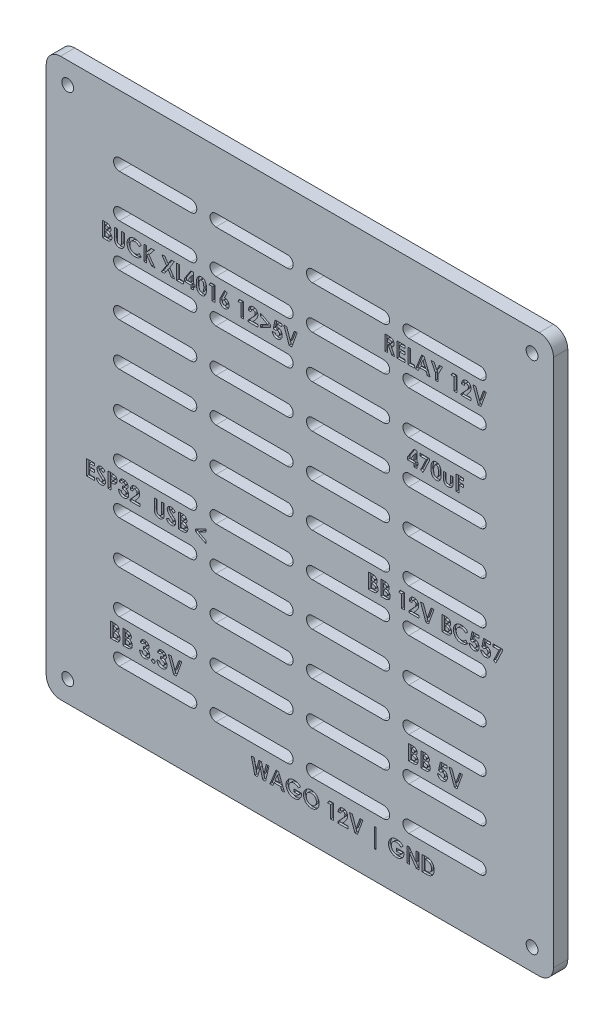
SolidWorks part; units mm, degrees
ref_plane "Front Plane" through (0, 0, 0) normal (0, 0, 1) x (1, 0, 0)
ref_plane "Top Plane" through (0, 0, 0) normal (0, 1, 0) x (1, 0, 0)
ref_plane "Right Plane" through (0, 0, 0) normal (1, 0, 0) x (0, 0, -1)
sketch "Sketch1" plane through (0, 0, 0) normal (0, 0, 1) x (1, 0, 0)
  line L0 (-67, 40) -> (67, 40)
  line L1 (71, 44) -> (71, 192)
  line L2 (67, 196) -> (-67, 196)
  line L3 (-71, 192) -> (-71, 44)
  arc A0 (-71, 44) -> (-67, 40) centre (-67, 44) ccw
  arc A1 (67, 40) -> (71, 44) centre (67, 44) ccw
  arc A2 (71, 192) -> (67, 196) centre (67, 192) ccw
  arc A3 (-67, 196) -> (-71, 192) centre (-67, 192) ccw
extrude "Plate" add sketch "Sketch1" along normal blind 4
sketch "Sketch2" plane through (0, 0, 0) normal (0, 0, 1) x (1, 0, 0)
  line L0 (-50.5, 58) -> (-30.5, 58) construction
  line L1 (-50.5, 59.65) -> (-30.5, 59.65)
  line L2 (-50.5, 56.35) -> (-30.5, 56.35)
  line L3 (-23.5, 58) -> (-3.5, 58) construction
  line L4 (-23.5, 59.65) -> (-3.5, 59.65)
  line L5 (-23.5, 56.35) -> (-3.5, 56.35)
  line L6 (3.5, 58) -> (23.5, 58) construction
  line L7 (3.5, 59.65) -> (23.5, 59.65)
  line L8 (3.5, 56.35) -> (23.5, 56.35)
  line L9 (30.5, 58) -> (50.5, 58) construction
  line L10 (30.5, 59.65) -> (50.5, 59.65)
  line L11 (30.5, 56.35) -> (50.5, 56.35)
  line L12 (-50.5, 70) -> (-30.5, 70) construction
  line L13 (-50.5, 71.65) -> (-30.5, 71.65)
  line L14 (-50.5, 68.35) -> (-30.5, 68.35)
  line L15 (-23.5, 70) -> (-3.5, 70) construction
  line L16 (-23.5, 71.65) -> (-3.5, 71.65)
  line L17 (-23.5, 68.35) -> (-3.5, 68.35)
  line L18 (3.5, 70) -> (23.5, 70) construction
  line L19 (3.5, 71.65) -> (23.5, 71.65)
  line L20 (3.5, 68.35) -> (23.5, 68.35)
  line L21 (30.5, 70) -> (50.5, 70) construction
  line L22 (30.5, 71.65) -> (50.5, 71.65)
  line L23 (30.5, 68.35) -> (50.5, 68.35)
  line L24 (-50.5, 82) -> (-30.5, 82) construction
  line L25 (-50.5, 83.65) -> (-30.5, 83.65)
  line L26 (-50.5, 80.35) -> (-30.5, 80.35)
  line L27 (-23.5, 82) -> (-3.5, 82) construction
  line L28 (-23.5, 83.65) -> (-3.5, 83.65)
  line L29 (-23.5, 80.35) -> (-3.5, 80.35)
  line L30 (3.5, 82) -> (23.5, 82) construction
  line L31 (3.5, 83.65) -> (23.5, 83.65)
  line L32 (3.5, 80.35) -> (23.5, 80.35)
  line L33 (30.5, 82) -> (50.5, 82) construction
  line L34 (30.5, 83.65) -> (50.5, 83.65)
  line L35 (30.5, 80.35) -> (50.5, 80.35)
  line L36 (-50.5, 94) -> (-30.5, 94) construction
  line L37 (-50.5, 95.65) -> (-30.5, 95.65)
  line L38 (-50.5, 92.35) -> (-30.5, 92.35)
  line L39 (-23.5, 94) -> (-3.5, 94) construction
  line L40 (-23.5, 95.65) -> (-3.5, 95.65)
  line L41 (-23.5, 92.35) -> (-3.5, 92.35)
  line L42 (3.5, 94) -> (23.5, 94) construction
  line L43 (3.5, 95.65) -> (23.5, 95.65)
  line L44 (3.5, 92.35) -> (23.5, 92.35)
  line L45 (30.5, 94) -> (50.5, 94) construction
  line L46 (30.5, 95.65) -> (50.5, 95.65)
  line L47 (30.5, 92.35) -> (50.5, 92.35)
  line L48 (-50.5, 106) -> (-30.5, 106) construction
  line L49 (-50.5, 107.65) -> (-30.5, 107.65)
  line L50 (-50.5, 104.35) -> (-30.5, 104.35)
  line L51 (-23.5, 106) -> (-3.5, 106) construction
  line L52 (-23.5, 107.65) -> (-3.5, 107.65)
  line L53 (-23.5, 104.35) -> (-3.5, 104.35)
  line L54 (3.5, 106) -> (23.5, 106) construction
  line L55 (3.5, 107.65) -> (23.5, 107.65)
  line L56 (3.5, 104.35) -> (23.5, 104.35)
  line L57 (30.5, 106) -> (50.5, 106) construction
  line L58 (30.5, 107.65) -> (50.5, 107.65)
  line L59 (30.5, 104.35) -> (50.5, 104.35)
  line L60 (-50.5, 118) -> (-30.5, 118) construction
  line L61 (-50.5, 119.65) -> (-30.5, 119.65)
  line L62 (-50.5, 116.35) -> (-30.5, 116.35)
  line L63 (-23.5, 118) -> (-3.5, 118) construction
  line L64 (-23.5, 119.65) -> (-3.5, 119.65)
  line L65 (-23.5, 116.35) -> (-3.5, 116.35)
  line L66 (3.5, 118) -> (23.5, 118) construction
  line L67 (3.5, 119.65) -> (23.5, 119.65)
  line L68 (3.5, 116.35) -> (23.5, 116.35)
  line L69 (30.5, 118) -> (50.5, 118) construction
  line L70 (30.5, 119.65) -> (50.5, 119.65)
  line L71 (30.5, 116.35) -> (50.5, 116.35)
  line L72 (-50.5, 130) -> (-30.5, 130) construction
  line L73 (-50.5, 131.65) -> (-30.5, 131.65)
  line L74 (-50.5, 128.35) -> (-30.5, 128.35)
  line L75 (-23.5, 130) -> (-3.5, 130) construction
  line L76 (-23.5, 131.65) -> (-3.5, 131.65)
  line L77 (-23.5, 128.35) -> (-3.5, 128.35)
  line L78 (3.5, 130) -> (23.5, 130) construction
  line L79 (3.5, 131.65) -> (23.5, 131.65)
  line L80 (3.5, 128.35) -> (23.5, 128.35)
  line L81 (30.5, 130) -> (50.5, 130) construction
  line L82 (30.5, 131.65) -> (50.5, 131.65)
  line L83 (30.5, 128.35) -> (50.5, 128.35)
  line L84 (-50.5, 142) -> (-30.5, 142) construction
  line L85 (-50.5, 143.65) -> (-30.5, 143.65)
  line L86 (-50.5, 140.35) -> (-30.5, 140.35)
  line L87 (-23.5, 142) -> (-3.5, 142) construction
  line L88 (-23.5, 143.65) -> (-3.5, 143.65)
  line L89 (-23.5, 140.35) -> (-3.5, 140.35)
  line L90 (3.5, 142) -> (23.5, 142) construction
  line L91 (3.5, 143.65) -> (23.5, 143.65)
  line L92 (3.5, 140.35) -> (23.5, 140.35)
  line L93 (30.5, 142) -> (50.5, 142) construction
  line L94 (30.5, 143.65) -> (50.5, 143.65)
  line L95 (30.5, 140.35) -> (50.5, 140.35)
  line L96 (-50.5, 154) -> (-30.5, 154) construction
  line L97 (-50.5, 155.65) -> (-30.5, 155.65)
  line L98 (-50.5, 152.35) -> (-30.5, 152.35)
  line L99 (-23.5, 154) -> (-3.5, 154) construction
  line L100 (-23.5, 155.65) -> (-3.5, 155.65)
  line L101 (-23.5, 152.35) -> (-3.5, 152.35)
  line L102 (3.5, 154) -> (23.5, 154) construction
  line L103 (3.5, 155.65) -> (23.5, 155.65)
  line L104 (3.5, 152.35) -> (23.5, 152.35)
  line L105 (30.5, 154) -> (50.5, 154) construction
  line L106 (30.5, 155.65) -> (50.5, 155.65)
  line L107 (30.5, 152.35) -> (50.5, 152.35)
  line L108 (-50.5, 166) -> (-30.5, 166) construction
  line L109 (-50.5, 167.65) -> (-30.5, 167.65)
  line L110 (-50.5, 164.35) -> (-30.5, 164.35)
  line L111 (-23.5, 166) -> (-3.5, 166) construction
  line L112 (-23.5, 167.65) -> (-3.5, 167.65)
  line L113 (-23.5, 164.35) -> (-3.5, 164.35)
  line L114 (3.5, 166) -> (23.5, 166) construction
  line L115 (3.5, 167.65) -> (23.5, 167.65)
  line L116 (3.5, 164.35) -> (23.5, 164.35)
  line L117 (30.5, 166) -> (50.5, 166) construction
  line L118 (30.5, 167.65) -> (50.5, 167.65)
  line L119 (30.5, 164.35) -> (50.5, 164.35)
  line L120 (-50.5, 178) -> (-30.5, 178) construction
  line L121 (-50.5, 179.65) -> (-30.5, 179.65)
  line L122 (-50.5, 176.35) -> (-30.5, 176.35)
  line L123 (-23.5, 178) -> (-3.5, 178) construction
  line L124 (-23.5, 179.65) -> (-3.5, 179.65)
  line L125 (-23.5, 176.35) -> (-3.5, 176.35)
  line L126 (3.5, 178) -> (23.5, 178) construction
  line L127 (3.5, 179.65) -> (23.5, 179.65)
  line L128 (3.5, 176.35) -> (23.5, 176.35)
  line L129 (30.5, 178) -> (50.5, 178) construction
  line L130 (30.5, 179.65) -> (50.5, 179.65)
  line L131 (30.5, 176.35) -> (50.5, 176.35)
  circle A0 centre (-65, 46) radius 1.65
  circle A1 centre (65, 46) radius 1.65
  circle A2 centre (-65, 190) radius 1.65
  circle A3 centre (65, 190) radius 1.65
  arc A4 (-50.5, 59.65) -> (-50.5, 56.35) centre (-50.5, 58) ccw
  arc A5 (-30.5, 56.35) -> (-30.5, 59.65) centre (-30.5, 58) ccw
  arc A6 (-23.5, 59.65) -> (-23.5, 56.35) centre (-23.5, 58) ccw
  arc A7 (-3.5, 56.35) -> (-3.5, 59.65) centre (-3.5, 58) ccw
  arc A8 (3.5, 59.65) -> (3.5, 56.35) centre (3.5, 58) ccw
  arc A9 (23.5, 56.35) -> (23.5, 59.65) centre (23.5, 58) ccw
  arc A10 (30.5, 59.65) -> (30.5, 56.35) centre (30.5, 58) ccw
  arc A11 (50.5, 56.35) -> (50.5, 59.65) centre (50.5, 58) ccw
  arc A12 (-50.5, 71.65) -> (-50.5, 68.35) centre (-50.5, 70) ccw
  arc A13 (-30.5, 68.35) -> (-30.5, 71.65) centre (-30.5, 70) ccw
  arc A14 (-23.5, 71.65) -> (-23.5, 68.35) centre (-23.5, 70) ccw
  arc A15 (-3.5, 68.35) -> (-3.5, 71.65) centre (-3.5, 70) ccw
  arc A16 (3.5, 71.65) -> (3.5, 68.35) centre (3.5, 70) ccw
  arc A17 (23.5, 68.35) -> (23.5, 71.65) centre (23.5, 70) ccw
  arc A18 (30.5, 71.65) -> (30.5, 68.35) centre (30.5, 70) ccw
  arc A19 (50.5, 68.35) -> (50.5, 71.65) centre (50.5, 70) ccw
  arc A20 (-50.5, 83.65) -> (-50.5, 80.35) centre (-50.5, 82) ccw
  arc A21 (-30.5, 80.35) -> (-30.5, 83.65) centre (-30.5, 82) ccw
  arc A22 (-23.5, 83.65) -> (-23.5, 80.35) centre (-23.5, 82) ccw
  arc A23 (-3.5, 80.35) -> (-3.5, 83.65) centre (-3.5, 82) ccw
  arc A24 (3.5, 83.65) -> (3.5, 80.35) centre (3.5, 82) ccw
  arc A25 (23.5, 80.35) -> (23.5, 83.65) centre (23.5, 82) ccw
  arc A26 (30.5, 83.65) -> (30.5, 80.35) centre (30.5, 82) ccw
  arc A27 (50.5, 80.35) -> (50.5, 83.65) centre (50.5, 82) ccw
  arc A28 (-50.5, 95.65) -> (-50.5, 92.35) centre (-50.5, 94) ccw
  arc A29 (-30.5, 92.35) -> (-30.5, 95.65) centre (-30.5, 94) ccw
  arc A30 (-23.5, 95.65) -> (-23.5, 92.35) centre (-23.5, 94) ccw
  arc A31 (-3.5, 92.35) -> (-3.5, 95.65) centre (-3.5, 94) ccw
  arc A32 (3.5, 95.65) -> (3.5, 92.35) centre (3.5, 94) ccw
  arc A33 (23.5, 92.35) -> (23.5, 95.65) centre (23.5, 94) ccw
  arc A34 (30.5, 95.65) -> (30.5, 92.35) centre (30.5, 94) ccw
  arc A35 (50.5, 92.35) -> (50.5, 95.65) centre (50.5, 94) ccw
  arc A36 (-50.5, 107.65) -> (-50.5, 104.35) centre (-50.5, 106) ccw
  arc A37 (-30.5, 104.35) -> (-30.5, 107.65) centre (-30.5, 106) ccw
  arc A38 (-23.5, 107.65) -> (-23.5, 104.35) centre (-23.5, 106) ccw
  arc A39 (-3.5, 104.35) -> (-3.5, 107.65) centre (-3.5, 106) ccw
  arc A40 (3.5, 107.65) -> (3.5, 104.35) centre (3.5, 106) ccw
  arc A41 (23.5, 104.35) -> (23.5, 107.65) centre (23.5, 106) ccw
  arc A42 (30.5, 107.65) -> (30.5, 104.35) centre (30.5, 106) ccw
  arc A43 (50.5, 104.35) -> (50.5, 107.65) centre (50.5, 106) ccw
  arc A44 (-50.5, 119.65) -> (-50.5, 116.35) centre (-50.5, 118) ccw
  arc A45 (-30.5, 116.35) -> (-30.5, 119.65) centre (-30.5, 118) ccw
  arc A46 (-23.5, 119.65) -> (-23.5, 116.35) centre (-23.5, 118) ccw
  arc A47 (-3.5, 116.35) -> (-3.5, 119.65) centre (-3.5, 118) ccw
  arc A48 (3.5, 119.65) -> (3.5, 116.35) centre (3.5, 118) ccw
  arc A49 (23.5, 116.35) -> (23.5, 119.65) centre (23.5, 118) ccw
  arc A50 (30.5, 119.65) -> (30.5, 116.35) centre (30.5, 118) ccw
  arc A51 (50.5, 116.35) -> (50.5, 119.65) centre (50.5, 118) ccw
  arc A52 (-50.5, 131.65) -> (-50.5, 128.35) centre (-50.5, 130) ccw
  arc A53 (-30.5, 128.35) -> (-30.5, 131.65) centre (-30.5, 130) ccw
  arc A54 (-23.5, 131.65) -> (-23.5, 128.35) centre (-23.5, 130) ccw
  arc A55 (-3.5, 128.35) -> (-3.5, 131.65) centre (-3.5, 130) ccw
  arc A56 (3.5, 131.65) -> (3.5, 128.35) centre (3.5, 130) ccw
  arc A57 (23.5, 128.35) -> (23.5, 131.65) centre (23.5, 130) ccw
  arc A58 (30.5, 131.65) -> (30.5, 128.35) centre (30.5, 130) ccw
  arc A59 (50.5, 128.35) -> (50.5, 131.65) centre (50.5, 130) ccw
  arc A60 (-50.5, 143.65) -> (-50.5, 140.35) centre (-50.5, 142) ccw
  arc A61 (-30.5, 140.35) -> (-30.5, 143.65) centre (-30.5, 142) ccw
  arc A62 (-23.5, 143.65) -> (-23.5, 140.35) centre (-23.5, 142) ccw
  arc A63 (-3.5, 140.35) -> (-3.5, 143.65) centre (-3.5, 142) ccw
  arc A64 (3.5, 143.65) -> (3.5, 140.35) centre (3.5, 142) ccw
  arc A65 (23.5, 140.35) -> (23.5, 143.65) centre (23.5, 142) ccw
  arc A66 (30.5, 143.65) -> (30.5, 140.35) centre (30.5, 142) ccw
  arc A67 (50.5, 140.35) -> (50.5, 143.65) centre (50.5, 142) ccw
  arc A68 (-50.5, 155.65) -> (-50.5, 152.35) centre (-50.5, 154) ccw
  arc A69 (-30.5, 152.35) -> (-30.5, 155.65) centre (-30.5, 154) ccw
  arc A70 (-23.5, 155.65) -> (-23.5, 152.35) centre (-23.5, 154) ccw
  arc A71 (-3.5, 152.35) -> (-3.5, 155.65) centre (-3.5, 154) ccw
  arc A72 (3.5, 155.65) -> (3.5, 152.35) centre (3.5, 154) ccw
  arc A73 (23.5, 152.35) -> (23.5, 155.65) centre (23.5, 154) ccw
  arc A74 (30.5, 155.65) -> (30.5, 152.35) centre (30.5, 154) ccw
  arc A75 (50.5, 152.35) -> (50.5, 155.65) centre (50.5, 154) ccw
  arc A76 (-50.5, 167.65) -> (-50.5, 164.35) centre (-50.5, 166) ccw
  arc A77 (-30.5, 164.35) -> (-30.5, 167.65) centre (-30.5, 166) ccw
  arc A78 (-23.5, 167.65) -> (-23.5, 164.35) centre (-23.5, 166) ccw
  arc A79 (-3.5, 164.35) -> (-3.5, 167.65) centre (-3.5, 166) ccw
  arc A80 (3.5, 167.65) -> (3.5, 164.35) centre (3.5, 166) ccw
  arc A81 (23.5, 164.35) -> (23.5, 167.65) centre (23.5, 166) ccw
  arc A82 (30.5, 167.65) -> (30.5, 164.35) centre (30.5, 166) ccw
  arc A83 (50.5, 164.35) -> (50.5, 167.65) centre (50.5, 166) ccw
  arc A84 (-50.5, 179.65) -> (-50.5, 176.35) centre (-50.5, 178) ccw
  arc A85 (-30.5, 176.35) -> (-30.5, 179.65) centre (-30.5, 178) ccw
  arc A86 (-23.5, 179.65) -> (-23.5, 176.35) centre (-23.5, 178) ccw
  arc A87 (-3.5, 176.35) -> (-3.5, 179.65) centre (-3.5, 178) ccw
  arc A88 (3.5, 179.65) -> (3.5, 176.35) centre (3.5, 178) ccw
  arc A89 (23.5, 176.35) -> (23.5, 179.65) centre (23.5, 178) ccw
  arc A90 (30.5, 179.65) -> (30.5, 176.35) centre (30.5, 178) ccw
  arc A91 (50.5, 176.35) -> (50.5, 179.65) centre (50.5, 178) ccw
  point P10 (-40.5, 58)
  point P15 (-13.5, 58)
  point P22 (13.5, 58)
  point P29 (40.5, 58)
  point P36 (-40.5, 70)
  point P43 (-13.5, 70)
  point P50 (13.5, 70)
  point P57 (40.5, 70)
  point P64 (-40.5, 82)
  point P71 (-13.5, 82)
  point P78 (13.5, 82)
  point P85 (40.5, 82)
  point P92 (-40.5, 94)
  point P99 (-13.5, 94)
  point P106 (13.5, 94)
  point P113 (40.5, 94)
  point P120 (-40.5, 106)
  point P127 (-13.5, 106)
  point P134 (13.5, 106)
  point P141 (40.5, 106)
  point P148 (-40.5, 118)
  point P155 (-13.5, 118)
  point P162 (13.5, 118)
  point P169 (40.5, 118)
  point P176 (-40.5, 130)
  point P183 (-13.5, 130)
  point P190 (13.5, 130)
  point P197 (40.5, 130)
  point P204 (-40.5, 142)
  point P211 (-13.5, 142)
  point P218 (13.5, 142)
  point P225 (40.5, 142)
  point P232 (-40.5, 154)
  point P239 (-13.5, 154)
  point P246 (13.5, 154)
  point P253 (40.5, 154)
  point P260 (-40.5, 166)
  point P267 (-13.5, 166)
  point P274 (13.5, 166)
  point P281 (40.5, 166)
  point P288 (-40.5, 178)
  point P295 (-13.5, 178)
  point P302 (13.5, 178)
  point P309 (40.5, 178)
  point P316 (0, 0)
extrude "Mounting slots" cut sketch "Sketch2" along normal through all
ref_plane "P1_Front_4" through (0, 0, 4) normal (0, 0, 1) x (1, 0, 0)
sketch "Sketch3" plane through (0, 0, 4) normal (0, 0, 1) x (1, 0, 0)
  text T0 "BUCK XL4016 12>5V" font "Century Gothic" height 4.2
  text T1 "RELAY 12V" font "Century Gothic" height 4.2
  text T2 "470uF" font "Century Gothic" height 4.2
  text T3 "ESP32  USB <" font "Century Gothic" height 4.2
  text T4 "WAGO 12V | GND" font "Century Gothic" height 4.2
  text T5 "BB 3.3V" font "Century Gothic" height 4.2
  text T6 "BB 5V" font "Century Gothic" height 4.2
  text T7 "BB 12V BC557" font "Century Gothic" height 4.2
extrude "Zone labels" cut sketch "Sketch3" against normal blind 0.6
